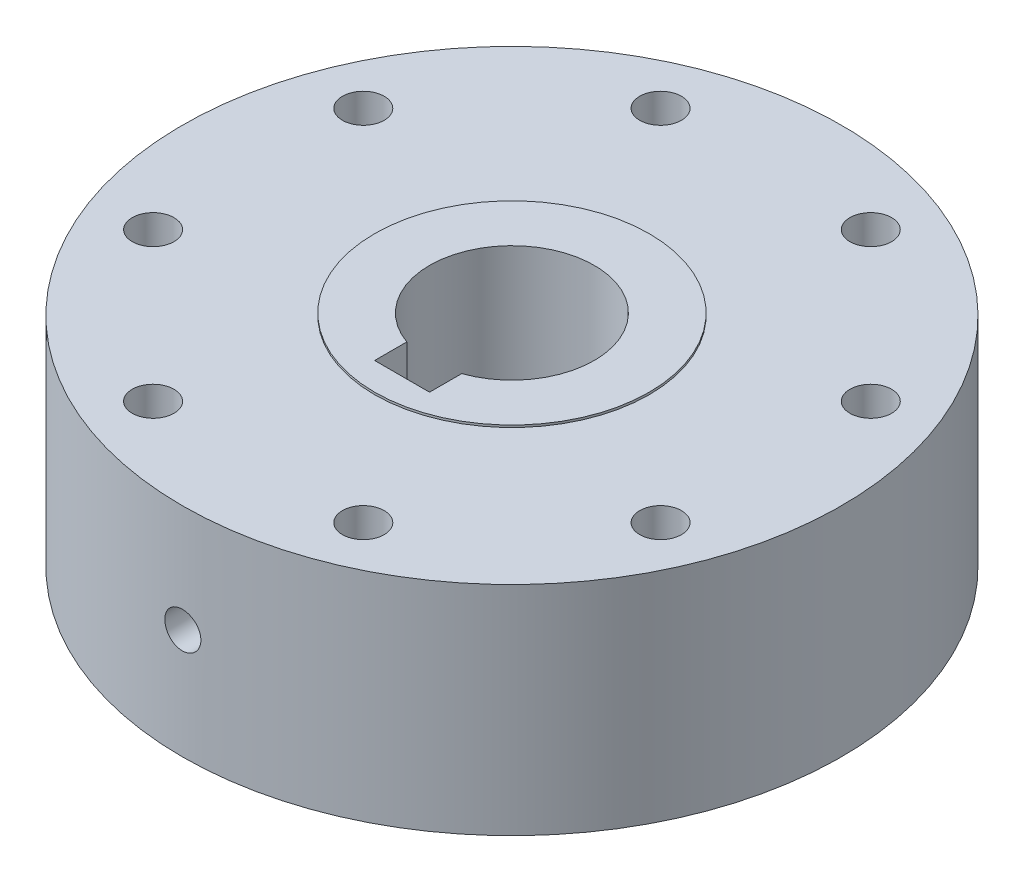
SolidWorks part; units mm, degrees
ref_plane "Front Plane" through (0, 0, 0) normal (0, 0, 1) x (1, 0, 0)
ref_plane "Top Plane" through (0, 0, 0) normal (0, 1, 0) x (1, 0, 0)
ref_plane "Right Plane" through (0, 0, 0) normal (1, 0, 0) x (0, 0, -1)
sketch "Sketch1" plane through (0, 0, 0) normal (0, 1, 0) x (1, 0, 0)
  circle A0 centre (0, 0) radius 38.1
  circle A1 centre (0, 0) radius 9.525
  dimension "D1" = 76.2
  dimension "D2" = 19.05
extrude "Boss-Extrude1" add sketch "Sketch1" along normal blind 25.4
hole_wizard "#10-32 Tapped Hole1" positions "Sketch3" profile "Sketch2" tap size "#10-32" standard "Ansi Inch" end condition through all
sketch "Sketch3" plane through (0, 25.4, 0) normal (0, 1, 0) x (-1, 0, 0)
  line L0 (38.1, 0) -> (0, 0) construction
  line L1 (0, 0) -> (29.3332, -12.1502) construction
  circle A0 centre (0, 0) radius 38.1 construction
  point P0 (29.3332, -12.1502)
  dimension "D1" = 31.75
  dimension "D2" = 22.5
sketch "Sketch2" plane through (-29.3332, 25.4, -12.1502) normal (1, 0, 0) x (0, 0, 1)
  line L0 (0, 0) -> (0, 25.4)
  line L1 (0, 25.4) -> (2.413, 25.4)
  line L2 (2.413, 25.4) -> (2.413, 0)
  line L5 (2.413, 0) -> (0, 0)
  line L11 (0, -6.35) -> (0, 107.95) construction
  dimension "Thread Major Dia." = 4.826
  dimension "Thru Tap Drill Depth" = 25.4
pattern_circular "CirPattern1" count 8 over 360 about axis through (0, 25.4, 0) along (0, -1, 0) of "#10-32 Tapped Hole1"
sketch "Sketch4" plane through (0, 25.4, 0) normal (0, 1, 0) x (1, 0, 0)
  line L1 (-3.175, -12.7) -> (3.175, -12.7)
  line L2 (-3.175, -12.7) -> (-3.175, -6.35)
  line L3 (-3.175, -6.35) -> (3.175, -6.35)
  line L4 (3.175, -12.7) -> (3.175, -6.35)
  line L5 (-3.175, -12.7) -> (3.175, -6.35) construction
  line L6 (-3.175, -6.35) -> (3.175, -12.7) construction
  circle A0 centre (0, 0) radius 9.525 construction
  point P0 (0, -9.525)
  dimension "D1" = 6.35
  dimension "D2" = 6.35
extrude "Cut-Extrude1" cut sketch "Sketch4" against normal through all
hole_wizard "#8-32 Tapped Hole1" positions "Sketch6" profile "Sketch5" tap size "#8-32" standard "Ansi Inch" end condition through all
sketch "Sketch6" plane through (0, 0, 12.7) normal (0, 0, -1) x (-1, 0, 0)
  line L0 (3.175, 0) -> (-3.175, 0) construction
  line L1 (3.175, 0) -> (3.175, 25.4) construction
  point P0 (0, 12.7)
  dimension "D1" = 12.7
  dimension "D2" = 3.175
sketch "Sketch5" plane through (0, 12.7, 12.7) normal (1, 0, 0) x (0, 1, 0)
  line L0 (0, 0) -> (0, 25.4)
  line L1 (0, 25.4) -> (2.0828, 25.4)
  line L2 (2.0828, 25.4) -> (2.0828, 0)
  line L5 (2.0828, 0) -> (0, 0)
  line L11 (0, -6.35) -> (0, 107.95) construction
  dimension "Thread Major Dia." = 4.1656
  dimension "Thru Tap Drill Depth" = 25.4
sketch "Sketch7" plane through (0, 25.4, 0) normal (0, 1, 0) x (1, 0, 0)
  circle A0 centre (0, 0) radius 15.875
  dimension "D1" = 31.75
extrude "Cut-Extrude2" cut sketch "Sketch7" against normal blind 0.254 flip side to cut
